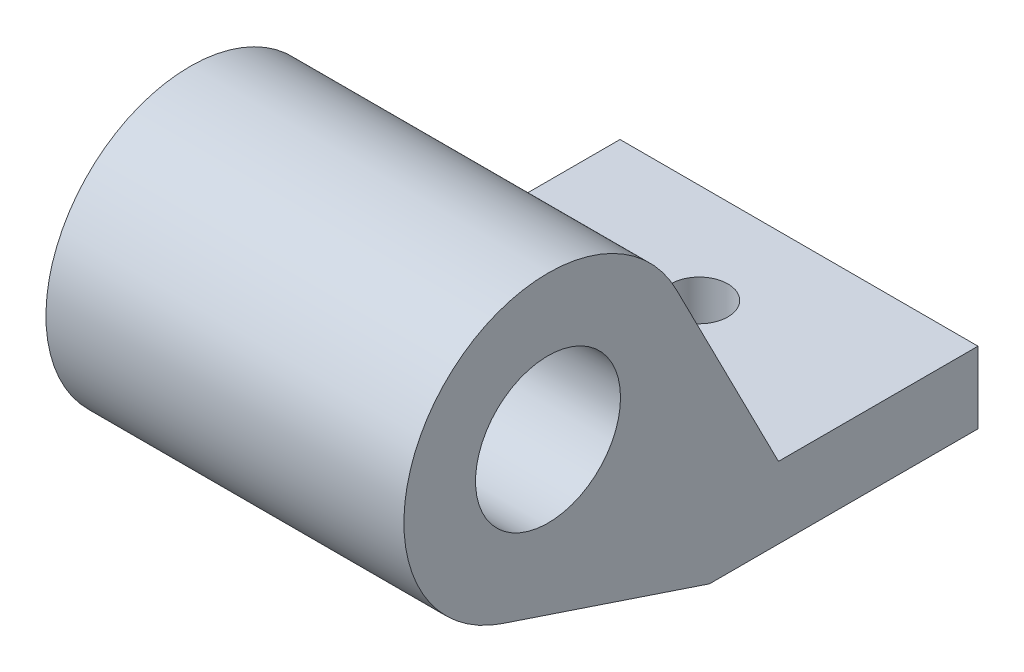
SolidWorks part; units mm, degrees
ref_plane "Front Plane" through (0, 0, 0) normal (0, 0, 1) x (1, 0, 0)
ref_plane "Top Plane" through (0, 0, 0) normal (0, 1, 0) x (1, 0, 0)
ref_plane "Right Plane" through (0, 0, 0) normal (1, 0, 0) x (0, 0, -1)
sketch "Sketch1" plane through (0, 0, 0) normal (1, 0, 0) x (0, 0, -1)
  line L0 (-7.5, 0) -> (7.5, 0)
  line L2 (-3.6484, 4) -> (7.5, 4)
  line L3 (7.5, 4) -> (7.5, 0)
  line L4 (-7.5, 0) -> (-19.072, 3.8636)
  line L5 (-3.6484, 4) -> (-9.3549, 15.1633)
  circle A0 centre (-16.5227, 11.4992) radius 4.05
  arc A1 (-9.3549, 15.1633) -> (-19.072, 3.8636) centre (-16.5227, 11.4992) ccw
  circle A2 centre (-16.5227, 11.4992) radius 8.05 construction
  point P5 (0, 0)
  dimension "D1" = 8.1
  dimension "D2" = 15
  dimension "D3" = 4
  dimension "D4" = 4
extrude "Boss-Extrude1" add sketch "Sketch1" along normal blind 20
sketch "Sketch2" plane through (0, 4, 0) normal (0, 1, 0) x (1, 0, 0)
  line L0 (20, 7.5) -> (20, -3.6484) construction
  line L1 (20, 7.5) -> (0, 7.5) construction
  circle A0 centre (10, 1.9258) radius 1.6
  point P4 (20, 1.9258)
  point P7 (10, 7.5)
  dimension "D1" = 3.2
extrude "Cut-Extrude1" cut sketch "Sketch2" against normal through all
